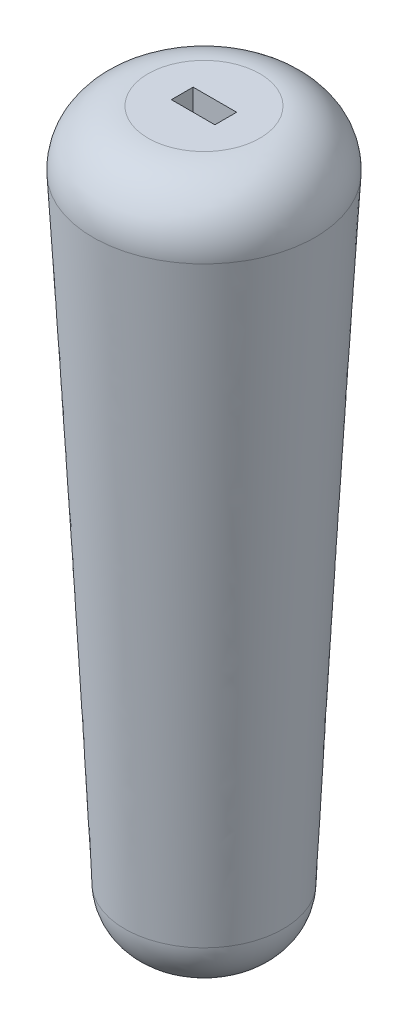
SolidWorks part; units mm, degrees
ref_plane "Front" through (0, 0, 0) normal (0, 0, 1) x (1, 0, 0)
ref_plane "Top" through (0, 0, 0) normal (0, 1, 0) x (1, 0, 0)
ref_plane "Right" through (0, 0, 0) normal (1, 0, 0) x (0, 0, -1)
sketch "Sketch1" plane through (0, 0, 0) normal (0, 1, 0) x (1, 0, 0)
  circle A0 centre (0, 0) radius 52.5796
  dimension "D1" = 105.1592
ref_plane "Plane2" through (0, -333.756, 0) normal (0, 1, 0) x (-1, 0, 0)
sketch "Sketch2" plane through (0, -333.756, 0) normal (0, 1, 0) x (-1, 0, 0)
  circle A0 centre (0, 0) radius 35.3901
  dimension "D1" = 70.7803
loft "Loft1" add profiles "Sketch1", "Sketch2" connector at (-51.426, 0, -10.9535) connector at (-30.5069, -333.756, -17.9384)
fillet "Fillet3" radius 25.4 2 edges at (0, 0, 52.5796) (0, -333.756, 35.3901)
sketch "Sketch3" plane through (0, -333.756, 0) normal (0, -1, 0) x (1, 0, 0)
  circle A0 centre (0, 0) radius 36.4634 construction
  point P0 (0, 0)
ref_axis "Axis1" through (0, 245.3766, 0) along (0, -1, 0)
sketch "Sketch5" plane through (0, -333.756, 0) normal (0, -1, 0) x (1, 0, 0)
  line L1 (-10, -5) -> (10, -5)
  line L2 (-10, -5) -> (-10, 5)
  line L3 (-10, 5) -> (10, 5)
  line L4 (10, -5) -> (10, 5)
  line L5 (-10, -5) -> (10, 5) construction
  line L6 (-10, 5) -> (10, -5) construction
  point P0 (0, 0)
  dimension "D1" = 20
  dimension "D2" = 10
extrude "Cut-Extrude2" cut sketch "Sketch5" against normal blind 12.7
sketch "Sketch4" plane through (0, 0, 0) normal (0, 1, 0) x (1, 0, 0)
  line L4 (10, 5) -> (-10, 5)
  line L5 (10, -5) -> (10, 5)
  line L6 (-10, -5) -> (10, -5)
  line L7 (-10, 5) -> (-10, -5)
  line L8 (10, 5) -> (-10, 5)
  line L9 (10, -5) -> (10, 5)
  line L10 (-10, -5) -> (10, -5)
  line L11 (-10, 5) -> (-10, -5)
  dimension "D1" = 0
extrude "Cut-Extrude1" cut sketch "Sketch4" against normal blind 12.7
